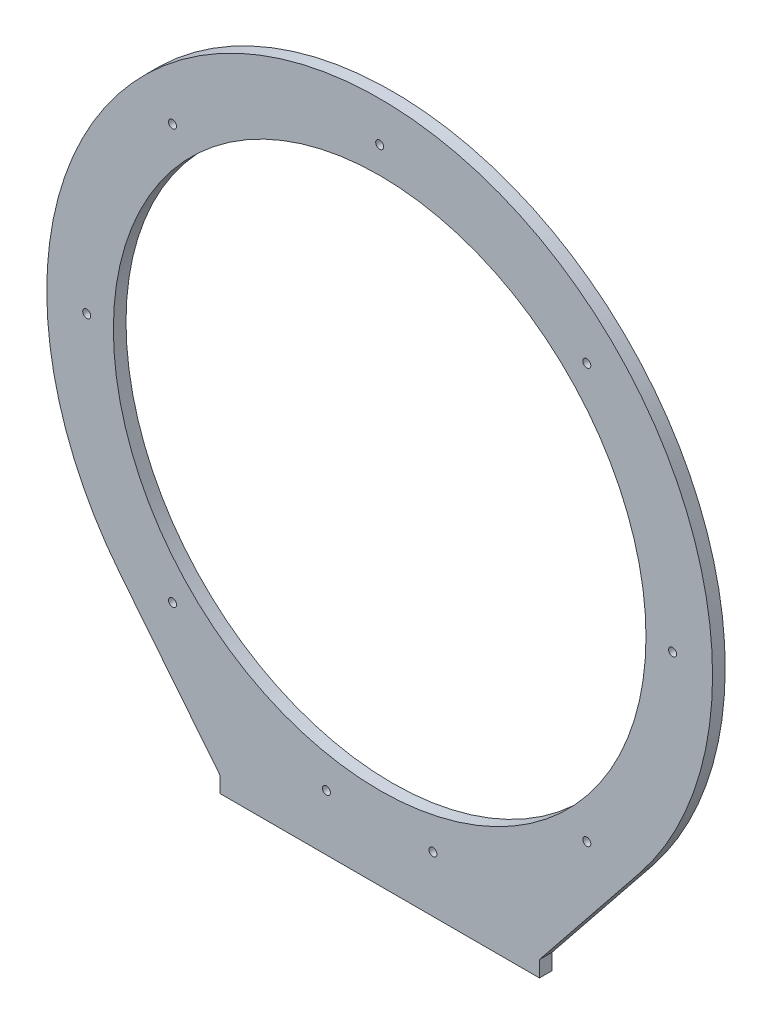
SolidWorks part; units mm, degrees
note: '?' marks a value the reader was unsure of.
ref_plane "Front Plane" through (0, 0, 0) normal (0, 0, 1) x (1, 0, 0)
ref_plane "Top Plane" through (0, 0, 0) normal (0, 1, 0) x (1, 0, 0)
ref_plane "Right Plane" through (0, 0, 0) normal (1, 0, 0) x (0, 0, -1)
sketch "Sketch1" plane through (0, 0, 0) normal (0, 0, 1) x (1, 0, 0)
  line L0 (0, 0) -> (88.3883, 88.3883) construction
  line L1 (0, 0) -> (88.3883, -88.3883) construction
  line L2 (0, 0) -> (0, -125) construction
  line L3 (0, 0) -> (125, 0) construction
  line L4 (0, -125) -> (0, -128) construction
  line L8 (-60, -125) -> (-60, -131)
  line L9 (-60, -131) -> (60, -131)
  line L10 (60, -125) -> (60, -131)
  line L11 (-60, -125) -> (60, -131) construction
  line L12 (-60, -131) -> (60, -125) construction
  line L15 (-60, -125) -> (-97.5293, -78.186)
  line L16 (60, -125) -> (97.5293, -78.186)
  circle A0 centre (0, 0) radius 100
  circle A3 centre (77.7817, -77.7817) radius 1.5
  circle A4 centre (77.7817, 77.7817) radius 1.5
  circle A6 centre (0, 110) radius 1.5
  circle A7 centre (-77.7817, -77.7817) radius 1.5
  circle A8 centre (-77.7817, 77.7817) radius 1.5
  circle A9 centre (110, 0) radius 1.5
  circle A10 centre (-110, 0) radius 1.5
  arc A11 (97.5293, -78.186) -> (-97.5293, -78.186) centre (0, 0) ccw
  circle A12 centre (-20, -110) radius 1.5
  circle A13 centre (20, -110) radius 1.5
  point P8 (77.7817, -77.7817)
  point P31 (0, -110)
  point P34 (-60, -125)
  point P37 (-60, -125)
  dimension "D1" = 15
  dimension "D2" = 15
  dimension "D4" = 15
  dimension "D5" = 250
  dimension "D6" = 60
extrude "Boss-Extrude1" add sketch "Sketch1" along normal blind 4.75
convert to sheet metal "Convert-Solid1" [suppressed] bend radius? 10 thickness? 4.75
sketch "Bend-Lines1" [suppressed] plane through (0, 0, 0) normal (0, 1, 0) x (1, 0, 0)
sketch "Bounding-Box1" [suppressed] plane through (0, 0, 0) normal (0, 1, 0) x (1, 0, 0)
sheet metal parameters "Sheet-Metal2" thickness 4.75 parameters "D1"=10
flat pattern "Flat-Pattern2" [suppressed]
sketch "Bend-Lines2" plane through (0, 0, 0) normal (0, 1, 0) x (1, 0, 0)
sketch3d "Bounding-Box2" [suppressed]
  line L0 (125, 125, 0) -> (125, -131, 0) construction
  line L1 (-125, 125, 0) -> (-125, -131, 0) construction
  line L2 (125, 125, 0) -> (-125, 125, 0) construction
  line L3 (125, -131, 0) -> (-125, -131, 0) construction
